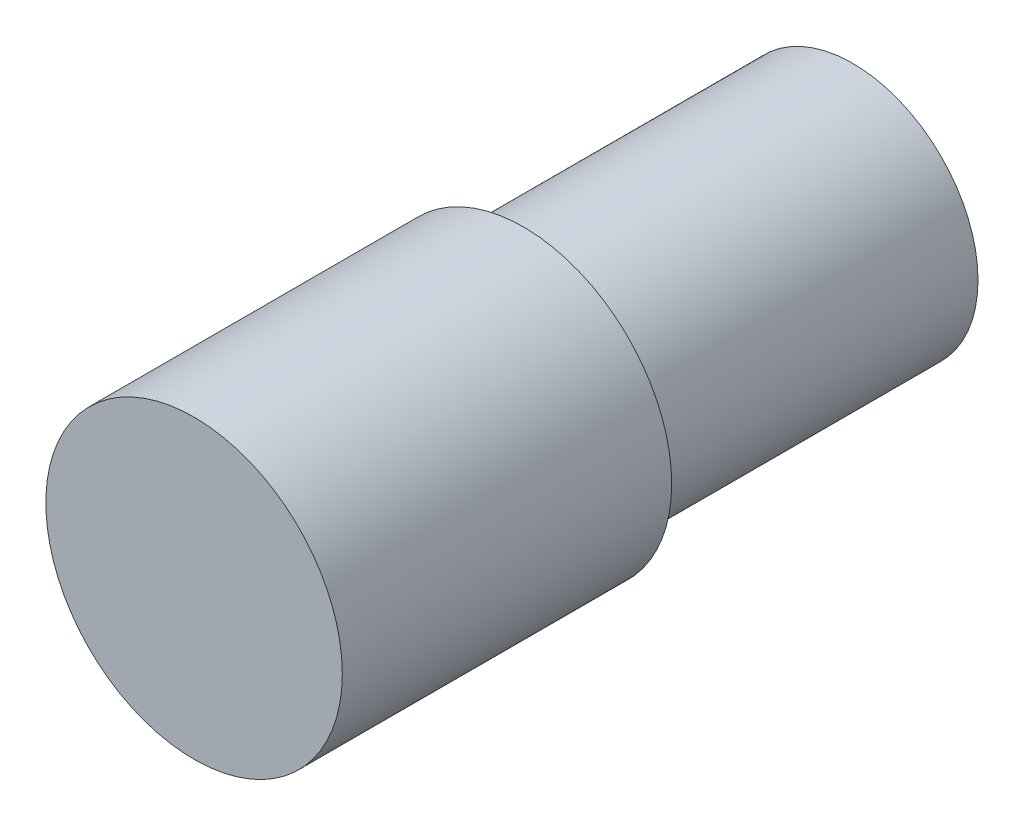
SolidWorks part; units mm, degrees
ref_plane "Front Plane" through (0, 0, 0) normal (0, 0, 1) x (1, 0, 0)
ref_plane "Top Plane" through (0, 0, 0) normal (0, 1, 0) x (1, 0, 0)
ref_plane "Right Plane" through (0, 0, 0) normal (1, 0, 0) x (0, 0, -1)
sketch "Sketch1" plane through (0, 0, 0) normal (0, 0, 1) x (1, 0, 0)
  circle A0 centre (0, 0) radius 3.8
extrude "Extrude1" add sketch "Sketch1" along normal blind 10
sketch "Sketch2" plane through (0, 0, 10) normal (0, 0, 1) x (1, 0, 0)
  circle A0 centre (0, 0) radius 4.5
extrude "Extrude2" add sketch "Sketch2" along normal blind 10
